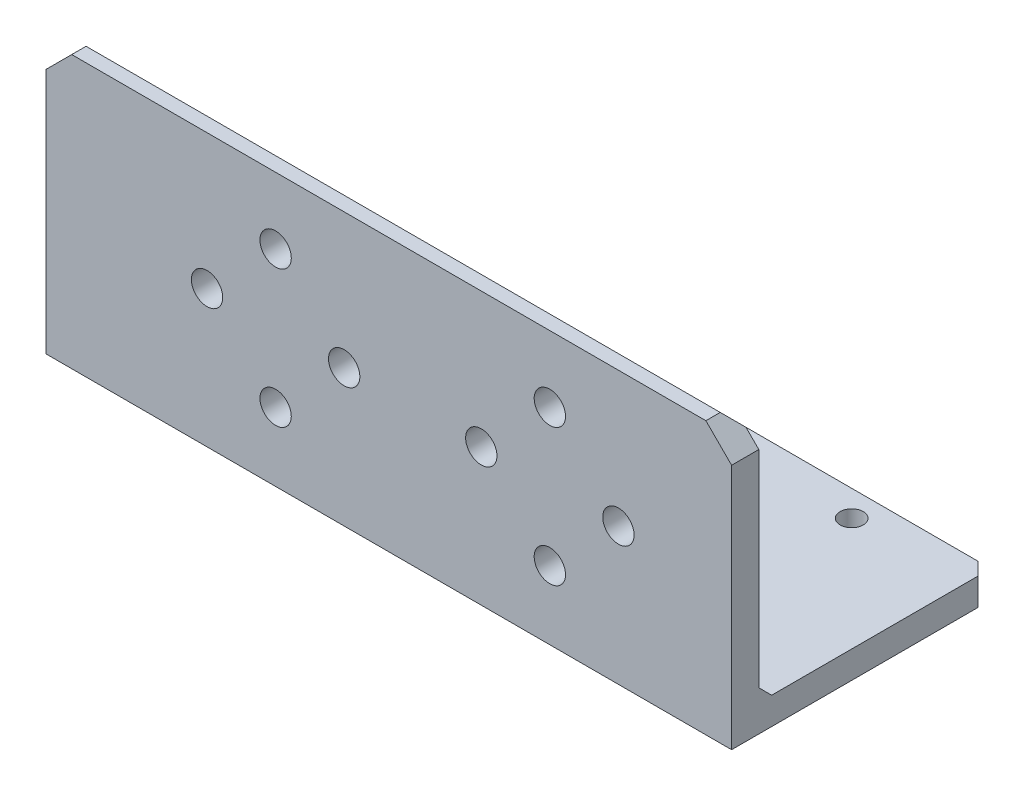
SolidWorks part; units mm, degrees
material "6061-T6 (SS)"
ref_plane "Front" through (0, 0, 0) normal (0, 0, 1) x (1, 0, 0)
ref_plane "Top" through (0, 0, 0) normal (0, 1, 0) x (1, 0, 0)
ref_plane "Right" through (0, 0, 0) normal (1, 0, 0) x (0, 0, -1)
ref_axis "side-side" through (80.9, 0, 0) along (-1, 0, 0)
ref_axis "up-down" through (0, 50, 0) along (0, -1, 0)
ref_axis "front-back" through (0, 0, -80.9) along (0, 0, 1)
sketch3d "3DSketch1"
  circle A8 centre (-128, 0, -19.221) radius 1.85
  circle A9 centre (-128, 0, -27.221) radius 4
  circle A10 centre (-120, 0, -27.221) radius 1.85
  circle A11 centre (-136, 0, -27.221) radius 1.85
  circle A12 centre (-128, 0, -11.221) radius 4
  circle A13 centre (-133.6569, 0, -0.8779) radius 1.85
  circle A14 centre (-122.3431, 0, -0.8779) radius 1.85
  circle A15 centre (-128, 0, -3.221) radius 1.85
  circle A24 centre (-21.208, 16, 0) radius 1.3525
  arc A25 (-14.416, 8.6084, 0) -> (-14.416, 7.3916, 0) centre (-13.208, 8, 0) ccw
  circle A26 centre (-5.208, 16, 0.2) radius 1.3525
  arc A27 (-14.416, 24.6084, 0) -> (-14.416, 23.3916, 0) centre (-13.208, 24, 0) ccw
  circle A28 centre (18.792, 8, 0) radius 1.3525
  arc A29 (25.584, 16.6084, 0) -> (25.584, 15.3916, 0) centre (26.792, 16, 0) ccw
  circle A30 centre (18.792, 24, 0) radius 1.3525
  arc A31 (9.584, 16.6084, 0.2) -> (9.584, 15.3916, 0.2) centre (10.792, 16, 0.2) ccw
  point P25 (-128, 1.85, -19.221)
  point P27 (-128, 4, -27.221)
  point P29 (-120, 1.85, -27.221)
  point P31 (-136, 1.85, -27.221)
  point P33 (-128, 4, -11.221)
  point P35 (-133.6569, 1.85, -0.8779)
  point P37 (-122.3431, 1.85, -0.8779)
  point P39 (-128, 1.85, -3.221)
  point P69 (-21.208, 16, -1.3525)
  point P70 (-13.208, 8, -1.3525)
  point P72 (-5.208, 16, -1.1525)
  point P73 (-13.208, 24, -1.3525)
  point P75 (18.792, 8, -1.3525)
  point P76 (26.792, 16, -1.3525)
  point P78 (18.792, 24, -1.3525)
  point P79 (10.792, 16, -1.1525)
sketch "Sketch7" plane through (0, 0, 0) normal (0, 1, 0) x (1, 0, 0)
  line L1 (-5.208, 27.221) -> (-21.208, 27.221) construction
  line L2 (-13.208, 27.221) -> (-13.208, 19.221) construction
  line L3 (-37.208, 48.0477) -> (-37.208, 27.221) construction
  line L4 (10.792, 48.0477) -> (10.792, 27.221) construction
  line L5 (26.792, 48.0477) -> (26.792, 27.221) construction
  line L6 (18.792, 40.0477) -> (18.792, 19.221) construction
  circle A0 centre (-13.208, 27.221) radius 8 construction
  point P3 (0, 0)
  point P21 (0, 0)
  point P22 (0, 0)
  point P23 (0, 0)
  dimension "D1" = 16
  dimension "D2" = 24
sketch "Sketch1" plane through (0, 0, 0) normal (1, 0, 0) x (0, 0, -1)
  line L1 (0, 0) -> (31.75, 0)
  line L2 (0, 0) -> (0, 31.75)
  line L3 (0, 31.75) -> (3.175, 31.75)
  line L4 (31.75, 0) -> (31.75, 3.175)
  line L7 (31.75, 3.175) -> (3.175, 3.175)
  line L8 (3.175, 31.75) -> (3.175, 3.175)
  point P1 (3.175, 17.4625)
  dimension "D1" = 3.175
  dimension "D2" = 31.75
extrude "Boss-Extrude1" add sketch "Sketch1" along normal mid plane 80
chamfer "Chamfer1" distance 1.5 angle 45 3 edges at (0, 3.175, -31.75) (0, 3.175, -3.175) (0, 31.75, -3.175)
chamfer "Chamfer2" distance 3 angle 45 4 edges at (-40, 31.75, -0.8375) (-40, 0.8375, -31.75) (40, 0.8375, -31.75) (40, 31.75, -0.8375)
hole_wizard "#6-32 Tapped Hole1" positions "Sketch3" profile "Sketch4" tap size "#6-32" standard "ANSI Inch" end condition through all
sketch "Sketch3" plane through (0, 3.175, 0) normal (0, 1, 0) x (1, 0, 0)
  line L0 (0, 0) -> (0, 68.5449) construction
  point P13 (-37.208, 27.221)
  point P15 (10.792, 27.221)
  point P17 (-5.208, 27.221)
  point P19 (-13.208, 19.221)
  point P21 (-21.208, 27.221)
  point P37 (18.792, 19.221)
  point P40 (26.792, 27.221)
sketch "Sketch4" plane through (-37.208, 3.175, -27.221) normal (1, 0, 0) x (0, 0, 1)
  line L0 (0, 0) -> (0, 3.175)
  line L1 (0, 3.175) -> (1.3525, 3.175)
  line L2 (1.3525, 3.175) -> (1.3525, 0)
  line L5 (1.3525, 0) -> (0, 0)
  line L11 (0, -6.35) -> (0, 107.95) construction
  dimension "Thread Major Dia." = 2.7051
  dimension "Thru Tap Drill Depth" = 3.175
hole_wizard "#6 Clearance Hole1" positions "Sketch5" profile "Sketch6" hole size "#6" standard "ANSI Inch" end condition through all
sketch "Sketch5" plane through (0, 0, -3.175) normal (0, 0, -1) x (-1, 0, 0)
  point P0 (-10.792, 16)
  point P3 (-18.792, 8)
  point P6 (-18.792, 24)
  point P9 (-26.792, 16)
  point P12 (13.208, 24)
  point P15 (5.208, 16)
  point P18 (13.208, 8)
  point P21 (21.208, 16)
sketch "Sketch6" plane through (10.792, 16, -3.175) normal (1, 0, 0) x (0, 1, 0)
  line L0 (0, 0) -> (0, 3.175)
  line L1 (0, 3.175) -> (1.8288, 3.175)
  line L2 (1.8288, 3.175) -> (1.8288, 0)
  line L5 (1.8288, 0) -> (0, 0)
  line L11 (0, -6.35) -> (0, 107.95) construction
  dimension "Thru Hole Dia." = 3.6576
  dimension "Thru Hole Depth" = 3.175
